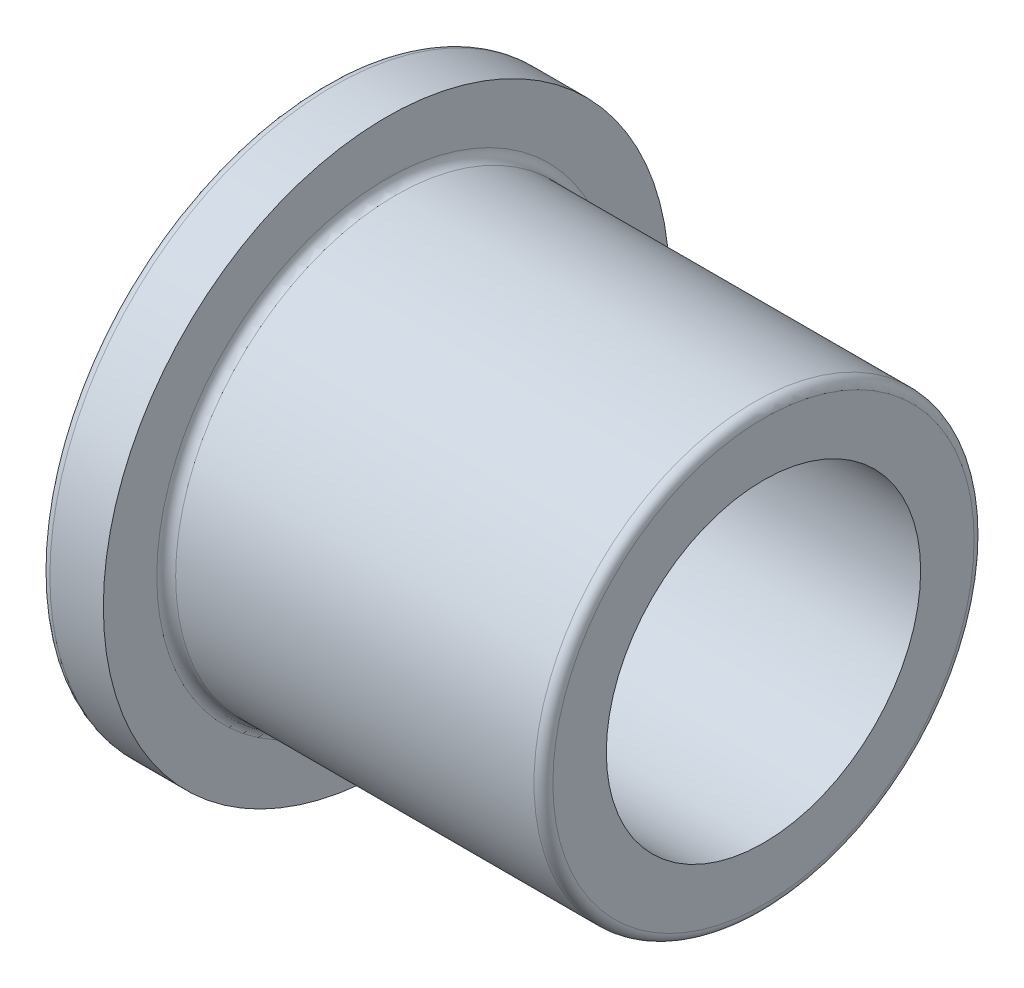
SolidWorks part; units mm, degrees
ref_plane "Front Plane" through (0, 0, 0) normal (0, 0, 1) x (1, 0, 0)
ref_plane "Top Plane" through (0, 0, 0) normal (0, 1, 0) x (1, 0, 0)
ref_plane "Right Plane" through (0, 0, 0) normal (1, 0, 0) x (0, 0, -1)
sketch "Sketch1" plane through (0, 0, 0) normal (1, 0, 0) x (0, 0, -1)
  circle A0 centre (0, 0) radius 7
  circle A1 centre (0, 0) radius 5
  dimension "D1" = 14
  dimension "D2" = 10
extrude "Boss-Extrude1" add sketch "Sketch1" against normal blind 12
sketch "Sketch2" plane through (-12, 0, 0) normal (-1, 0, 0) x (0, 0, 1)
  circle A0 centre (0, 0) radius 5 construction
  circle A1 centre (0, 0) radius 5
  circle A2 centre (0, 0) radius 9
  dimension "D1" = 18
extrude "Boss-Extrude2" add sketch "Sketch2" along normal blind 2
fillet "Fillet1" radius 0.3 3 edges at (-14, 0, 9) (0, 0, -7) (-12, 0, -7)
scale "Scale1" scale about centroid uniform scaling yes scale factor 0.317565
